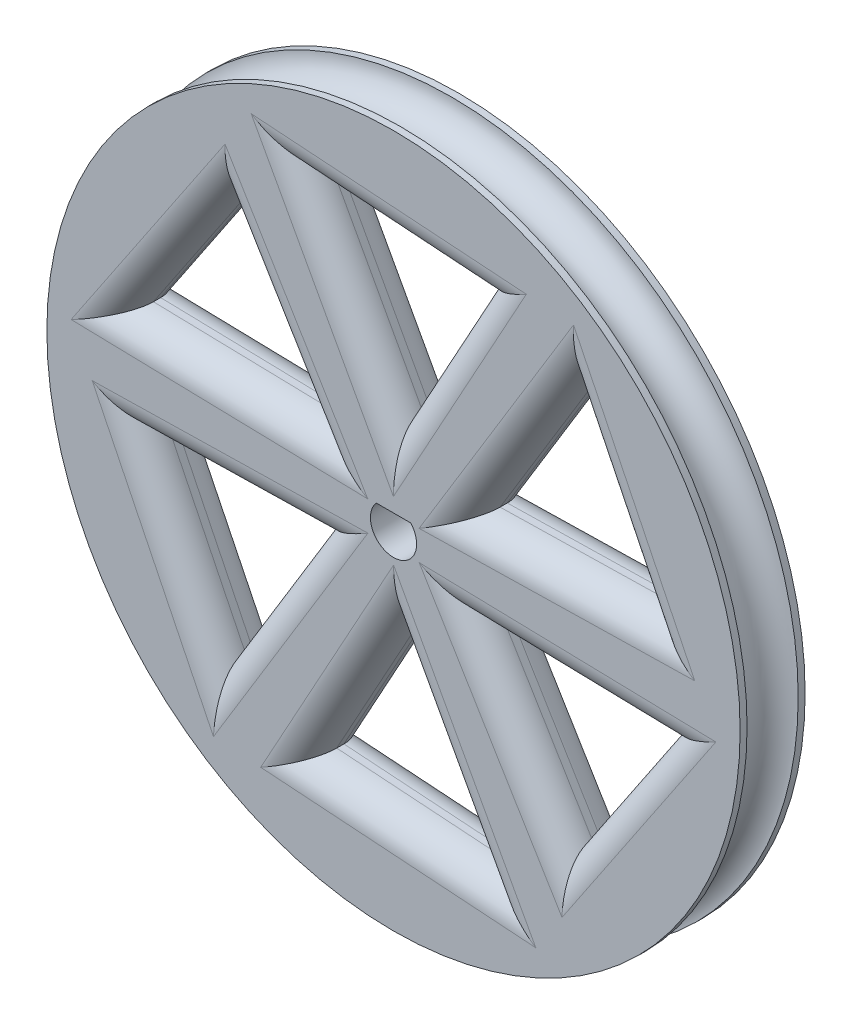
SolidWorks part; units mm, degrees
ref_plane "Front Plane" through (0, 0, 0) normal (0, 0, 1) x (1, 0, 0)
ref_plane "Top Plane" through (0, 0, 0) normal (0, 1, 0) x (1, 0, 0)
ref_plane "Right Plane" through (0, 0, 0) normal (1, 0, 0) x (0, 0, -1)
sketch "Sketch4" plane through (0, 0, 0) normal (1, 0, 0) x (0, 0, -1)
  line L0 (4.02, 24) -> (4.5, 24)
  line L1 (0, 0) -> (4.5, 0)
  line L2 (0, 0) -> (0, 24)
  line L3 (0, 24) -> (0.48, 24)
  line L4 (4.5, 0) -> (4.5, 24)
  arc A0 (0.48, 24) -> (4.02, 24) centre (2.25, 24) ccw
  dimension "D3" = 3.54
  dimension "D1" = 4.5
  dimension "D2" = 24
revolve "Revolve1" add sketch "Sketch4" angle 360 about L1
sketch "Sketch5" plane through (0, 0, 0) normal (0, 0, 1) x (1, 0, 0)
  line L3 (-1.1926, 1.0667) -> (1.1926, 1.0667)
  arc A0 (-1.1926, 1.0667) -> (1.1926, 1.0667) centre (0, 0) ccw
  dimension "D1" = 3.2
extrude "Cut-Extrude2" cut sketch "Sketch5" against normal blind 5
sketch "Sketch6" plane through (0, 0, 0) normal (0, 0, 1) x (1, 0, 0)
  line L0 (0, 6.2104) -> (-6.35, 17.8373)
  line L1 (-6.35, 17.8373) -> (5.9324, 16.9978)
  line L2 (5.9324, 16.9978) -> (0, 6.2104)
extrude "Cut-Extrude3" cut sketch "Sketch6" against normal blind 5
pattern_circular "CirPattern2" count 6 every 60 about axis through (0, 0, 0) along (0, 0, 1) of "Cut-Extrude3"
fillet "Fillet10" radius 2 1 edges at (-3.175, 12.0238, 0)
fillet "Fillet11" radius 2 1 edges at (-8.5663, 8.3709, 0)
fillet "Fillet12" radius 2 1 edges at (-14.5734, 9.4429, 0)
fillet "Fillet13" radius 2 1 edges at (-12.0004, 3.2623, 0)
fillet "Fillet14" radius 2 1 edges at (2.3945, 10.5646, 0)
fillet "Fillet15" radius 2 1 edges at (8.8255, 8.7615, 0)
fillet "Fillet16" radius 2 1 edges at (10.3464, 3.2085, 0)
fillet "Fillet17" radius 2 1 edges at (-0.2925, 17.4233, 0)
fillet "Fillet18" radius 2 1 edges at (14.9428, 8.9649, 0)
fillet "Fillet19" radius 2 1 edges at (12.0004, -3.2623, 0)
fillet "Fillet20" radius 2 1 edges at (7.9519, -7.356, 0)
fillet "Fillet21" radius 2 8 edges at (-14.9797, -8.8896, -4.5) (-14.9797, -8.8896, 0) (-11.5325, -3.2332, 0) (-8.8255, -8.7615, -4.5) (-2.9662, -11.6041, 0) (0.2088, -17.4175, 0) (3.175, -12.0238, -4.5) (15.2352, -8.4584, 0)
fillet "Fillet22" radius 2 1 edges at (3.175, -12.0238, 0)
fillet "Fillet23" radius 2 1 edges at (-8.8255, -8.7615, 0)
fillet "Fillet24" radius 2 15 edges at (1.3924, -17.4984, -4.5) (-2.3945, -10.5646, -4.5) (-11.4487, -3.2315, -4.5) (-12.0004, 3.2623, -4.5) (-15.1884, 8.528, -4.5) (-8.5663, 8.3709, -4.5) (-3.175, 12.0238, -4.5) (-0.2088, 17.4175, -4.5) (2.9662, 11.6041, -4.5) (8.8255, 8.7615, -4.5) (14.9797, 8.8896, -4.5) (11.5325, 3.2332, -4.5) (8.5663, -8.3709, -4.5) (12.0004, -3.2623, -4.5) (15.1884, -8.528, -4.5)
